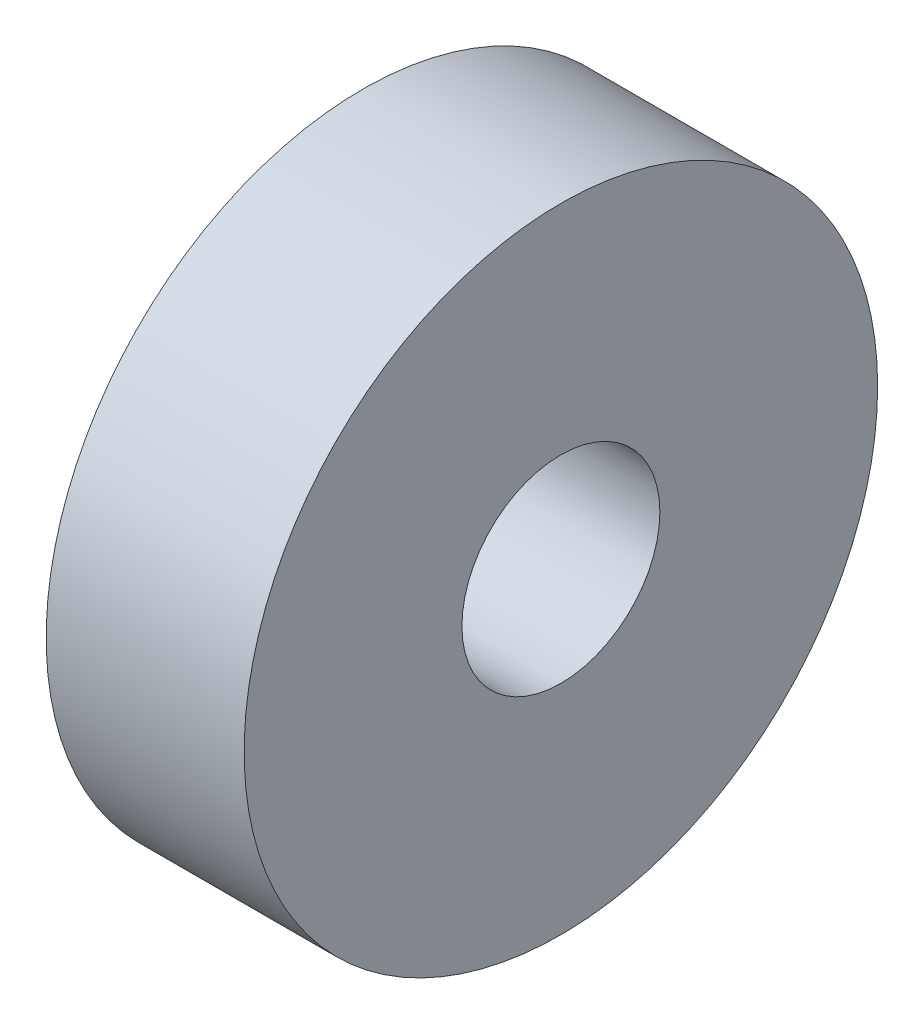
SolidWorks part; units mm, degrees
ref_plane "Front Plane" through (0, 0, 0) normal (0, 0, 1) x (1, 0, 0)
ref_plane "Top Plane" through (0, 0, 0) normal (0, 1, 0) x (1, 0, 0)
ref_plane "Right Plane" through (0, 0, 0) normal (1, 0, 0) x (0, 0, -1)
sketch "Sketch1" plane through (0, 0, 0) normal (1, 0, 0) x (0, 0, -1)
  circle A0 centre (0, 0) radius 2.5
  circle A1 centre (0, 0) radius 8
  dimension "D1" = 16
  dimension "D2" = 5
extrude "Boss-Extrude1" add sketch "Sketch1" along normal mid plane 5
move or copy body "Body-Move/Copy1" [suppressed] bodies to move or copy 101
